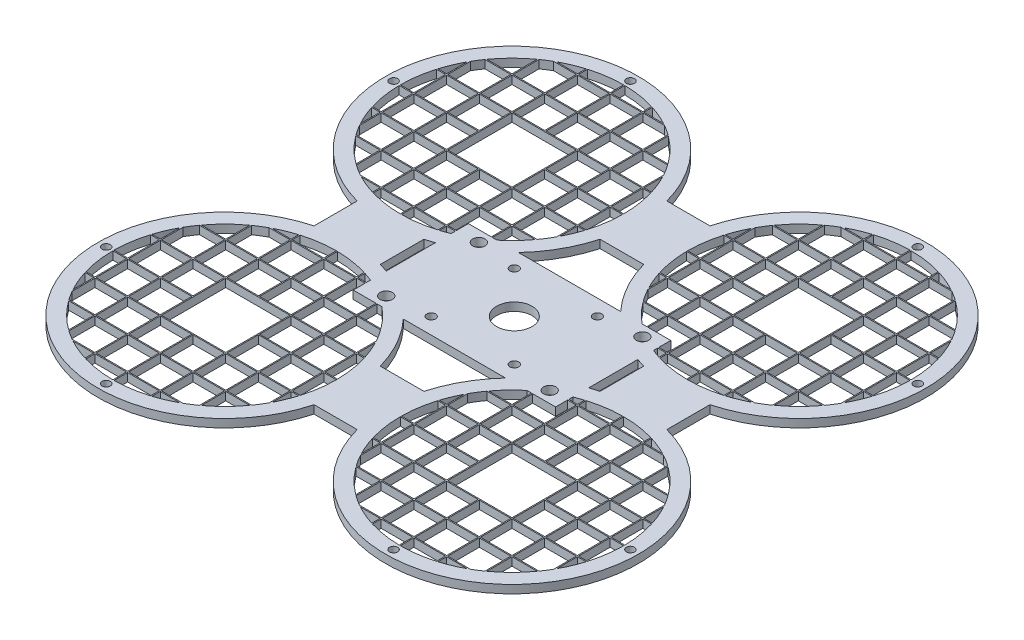
SolidWorks part; units mm, degrees
ref_plane "Front Plane" through (0, 0, 0) normal (0, 0, 1) x (1, 0, 0)
ref_plane "Top Plane" through (0, 0, 0) normal (0, 1, 0) x (1, 0, 0)
ref_plane "Right Plane" through (0, 0, 0) normal (1, 0, 0) x (0, 0, -1)
sketch "Sketch2" plane through (0, 0, 0) normal (0, 1, 0) x (1, 0, 0)
  circle A1 centre (0, 0) radius 41
  circle A2 centre (0, 0) radius 46
  point P208 (0, 0)
extrude "Boss-Extrude2" add sketch "Sketch2" along normal blind 3
sketch "Sketch4" plane through (0, 3, 0) normal (0, 1, 0) x (1, 0, 0)
  line L0 (0, 46) -> (0, 12)
  line L1 (12, 44.4072) -> (12, -44.4072)
  line L2 (24, 39.2428) -> (24, -39.2428)
  line L3 (36, 28.6356) -> (36, -28.6356)
  line L4 (-12, 44.4072) -> (-12, -44.4072)
  line L5 (-24, 39.2428) -> (-24, -32)
  line L6 (-36, 28.6356) -> (-36, -28.6356)
  line L7 (-46, 0) -> (-12, 0)
  line L8 (-44.4072, -12) -> (44.4072, -12)
  line L9 (-39.2428, -24) -> (39.2428, -24)
  line L10 (12, 0) -> (46, 0)
  line L11 (-44.4072, 12) -> (44.4072, 12)
  line L12 (-39.2428, 24) -> (39.2428, 24)
  line L13 (-28.6356, 36) -> (28.6356, 36)
  line L14 (-16, -36) -> (28.6356, -36)
  line L15 (0, -12) -> (0, -46)
  line L50 (-26.0661, -32) -> (-16, -32)
  line L52 (-26.0661, -32) -> (-26.0661, -37.902)
  line L60 (-16, -32) -> (-16, -43.1277)
  line L61 (-28.6356, -36) -> (-26.0661, -36) [skipped]
  circle A1 centre (0, 0) radius 46 construction
  circle A2 centre (0, 0) radius 46
  dimension "D1" = 4
  dimension "D2" = 4
extrude "Extrude-Thin5" add sketch "Sketch4" against normal blind 3 thin thin type one direction wall 0.4
sketch "Sketch5" plane through (0, 0, 0) normal (0, -1, 0) x (1, 0, 0)
  circle A0 centre (0, -43.4524) radius 1.5
  circle A3 centre (43.4524, 0) radius 1.5
  circle A4 centre (0, 43.4524) radius 1.5 [skipped]
  circle A5 centre (-43.4524, 0) radius 1.5 [skipped]
  point P11 (0, 0)
  dimension "D1" = 4
extrude "Cut-Extrude1" cut sketch "Sketch5" against normal blind 3
sketch "Sketch8" plane through (0, 3, 0) normal (0, 1, 0) x (1, 0, 0)
  line L1 (-16, -32) -> (-25.632, -32)
  line L2 (-16, -32) -> (-16, -37.7492)
  line L3 (-16, -37.7492) -> (-25.632, -37.7492)
  line L4 (-25.632, -32) -> (-25.632, -37.7492)
extrude "Boss-Extrude4" add sketch "Sketch8" against normal through all
sketch "Sketch9" plane through (0, 3, 0) normal (0, 1, 0) x (1, 0, 0)
  circle A3 centre (-22.2697, -36.1812) radius 2.25
extrude "Cut-Extrude3" cut sketch "Sketch9" against normal through all
ref_plane "Plane1" through (-52.73, 0, 0) normal (1, 0, 0) x (0, 0, -1)
mirror "Mirror1" about plane through (-52.73, 0, 0) normal (1, 0, 0) of bodies 159
sketch "Sketch10" plane through (0, 3, 0) normal (0, 1, 0) x (1, 0, 0)
  line L0 (-66.2554, 12) -> (-69.06, 12) construction
  line L1 (-63.5152, 12) -> (-41.7915, 12)
  line L2 (-63.5152, 12) -> (-63.5152, -12.4)
  line L3 (-63.5152, -12.4) -> (-41.7915, -12.4)
  line L4 (-41.7915, 12) -> (-41.7915, -12.4)
  line L5 (-66.3801, -12.4) -> (-69.06, -12.4) construction
extrude "Boss-Extrude5" add sketch "Sketch10" against normal up to surface (3 mm away) up to face at (-22.2697, 0, 38.4312)
ref_plane "Plane2" through (0, 0, 52.73) normal (0, 0, 1) x (1, 0, 0)
mirror "Mirror2" about plane through (0, 0, 52.73) normal (0, 0, 1) of bodies 177
sketch "Sketch11" plane through (0, 3, 0) normal (0, 1, 0) x (1, 0, 0)
  line L0 (-93.06, -36.4) -> (-93.06, -39.0799) construction
  line L1 (-117.46, -41.6571) -> (-93.06, -41.6571)
  line L2 (-117.46, -41.6571) -> (-117.46, -63.409)
  line L3 (-117.46, -63.409) -> (-93.06, -63.409)
  line L4 (-93.06, -41.6571) -> (-93.06, -63.409)
  line L5 (-117.46, -36.4) -> (-117.46, -39.2046) construction
extrude "Boss-Extrude6" add sketch "Sketch11" against normal up to surface (3 mm away) up to face at (-52.73, 0, -0.0036)
sketch "Sketch12" plane through (0, 3, 0) normal (0, 1, 0) x (1, 0, 0)
  line L0 (12, -36.4) -> (12, -39.2046) construction
  line L1 (-12.4, -42.0227) -> (12, -42.0227)
  line L2 (-12.4, -42.0227) -> (-12.4, -63.5098)
  line L3 (-12.4, -63.5098) -> (12, -63.5098)
  line L4 (12, -42.0227) -> (12, -63.5098)
  line L5 (-12.4, -36.4) -> (-12.4, -39.0799) construction
extrude "Boss-Extrude7" add sketch "Sketch12" against normal up to surface (3 mm away) up to face at (-62.5401, 0, 52.73)
sketch "Sketch13" plane through (0, 0, 0) normal (0, -1, 0) x (1, 0, 0)
  line L1 (-89.86, 73.86) -> (-15.6, 73.86)
  line L2 (-89.86, 73.86) -> (-89.86, 31.6)
  line L3 (-89.86, 31.6) -> (-15.6, 31.6)
  line L4 (-15.6, 73.86) -> (-15.6, 31.6)
extrude "Boss-Extrude8" add sketch "Sketch13" against normal up to surface (3 mm away) up to face at (-52.73, 3, 52.73)
sketch "Sketch14" plane through (0, 0, 0) normal (0, -1, 0) x (1, 0, 0)
  circle A0 centre (-51.9521, 52.6625) radius 6.495 construction
  circle A1 centre (-51.9521, 52.6625) radius 6.495
extrude "Cut-Extrude4" cut sketch "Sketch14" against normal up to next
sketch "Sketch15" plane through (0, 0, 0) normal (0, -1, 0) x (1, 0, 0)
  circle A0 centre (-36.702, 37.4126) radius 1.6 construction
  circle A1 centre (-67.202, 37.4124) radius 1.6 construction
  circle A2 centre (-67.2022, 67.9124) radius 1.6 construction
  circle A3 centre (-36.7022, 67.9126) radius 1.6 construction
  circle A4 centre (-36.702, 37.4126) radius 1.6
  circle A5 centre (-67.202, 37.4124) radius 1.6
  circle A6 centre (-67.2022, 67.9124) radius 1.6
  circle A7 centre (-36.7022, 67.9126) radius 1.6
extrude "Cut-Extrude5" cut sketch "Sketch15" against normal up to next
ref_plane "Plane3" through (-32.452, 23.8804, 37.4126) normal (0, 0, 1) x (1, 0, 0)
ref_plane "Plane4" through (-43.3021, 7.6858, 53.1026) normal (0, 0, 1) x (1, 0, 0)
sketch "Sketch18" plane through (0, 0, 0) normal (0, -1, 0) x (1, 0, 0)
  circle A0 centre (-21.9522, 69.6627) radius 2.25 construction
  circle A1 centre (-21.952, 35.6627) radius 2.25 construction
  circle A2 centre (-81.952, 35.6623) radius 2.25 construction
  circle A3 centre (-81.9522, 69.6623) radius 2.25 construction
  circle A4 centre (-21.9522, 69.6627) radius 2.25
  circle A5 centre (-21.952, 35.6627) radius 2.25
  circle A6 centre (-81.952, 35.6623) radius 2.25
  circle A7 centre (-81.9522, 69.6623) radius 2.25
extrude "Cut-Extrude6" cut sketch "Sketch18" against normal up to next
